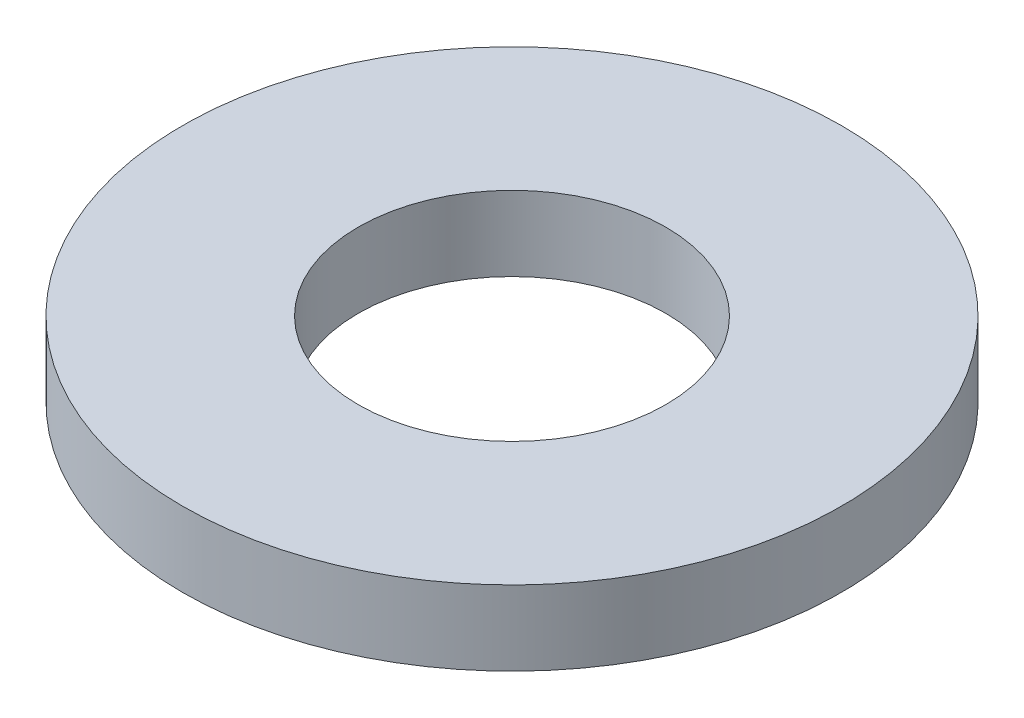
SolidWorks part; units mm, degrees
ref_plane "Front Plane" through (0, 0, 0) normal (0, 0, 1) x (1, 0, 0)
ref_plane "Top Plane" through (0, 0, 0) normal (0, 1, 0) x (1, 0, 0)
ref_plane "Right Plane" through (0, 0, 0) normal (1, 0, 0) x (0, 0, -1)
sketch "Sketch1" plane through (0, 0, 0) normal (0, 1, 0) x (1, 0, 0)
  circle A0 centre (0, 0) radius 75
  dimension "FLANGE_OD" = 150
extrude "Boss-Extrude1" add sketch "Sketch1" along normal blind 17
sketch "Sketch2" plane through (0, 0, 0) normal (0, 1, 0) x (1, 0, 0)
  circle A0 centre (0, 0) radius 35
  dimension "BORE_D" = 70
extrude "Cut-Extrude1" cut sketch "Sketch2" along normal through all
sketch "Sketch3" plane through (0, 17, 0) normal (0, 1, 0) x (1, 0, 0)
  circle A0 centre (0, 0) radius 30.1828 construction
  circle A1 centre (-30.1828, 0) radius 3.4356
  dimension "BOLT_D" = 6.8713
  dimension "BOLT_PCD" = 60.3655
extrude "Cut-Extrude2" cut sketch "Sketch3" against normal blind 14.1447 rebuild error yes
pattern_circular "CirPattern1" count 3 over 360 rebuild error yes
